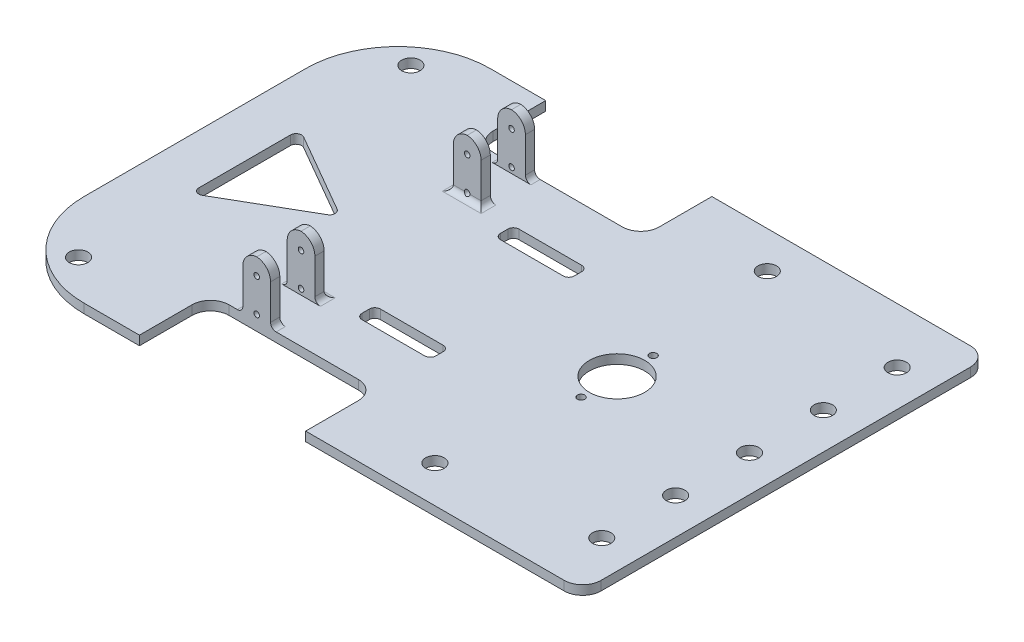
SolidWorks part; units mm, degrees
ref_plane "Front Plane" through (0, 0, 0) normal (0, 0, 1) x (1, 0, 0)
ref_plane "Top Plane" through (0, 0, 0) normal (0, 1, 0) x (1, 0, 0)
ref_plane "Right Plane" through (0, 0, 0) normal (1, 0, 0) x (0, 0, -1)
sketch "Sketch1" plane through (0, 0, 0) normal (0, 1, 0) x (1, 0, 0)
  line L1 (-160, 110) -> (160, 110)
  line L2 (-160, 110) -> (-160, -110)
  line L3 (-160, -110) -> (160, -110)
  line L4 (160, 110) -> (160, -110)
  line L5 (-160, 110) -> (160, -110) construction
  line L6 (-160, -110) -> (160, 110) construction
  point P1 (0, 0)
  dimension "D1" = 320
  dimension "D2" = 220
extrude "Boss-Extrude1" add sketch "Sketch1" along normal mid plane 5
sketch "Sketch2" plane through (0, 0, 0) normal (0, 1, 0) x (1, 0, 0)
  line L0 (0, 110) -> (0, -110) construction
  line L1 (160, 110) -> (-160, 110) construction
  line L2 (-160, -110) -> (160, -110) construction
  line L3 (160, 0) -> (-160, 0) construction
  line L4 (160, -110) -> (160, 110) construction
  line L5 (-160, 110) -> (-160, -110) construction
  line L6 (-133, 90) -> (-133, 0) construction
  line L7 (-133, -90) -> (-133, 0) construction
  line L8 (-160, 110) -> (-160, -110) construction
  line L10 (60, 90) -> (60, -90) construction
  line L11 (160, -110) -> (160, 110) construction
  circle A0 centre (-133, 90) radius 5
  circle A1 centre (-133, -90) radius 5
  circle A2 centre (60, 90) radius 5
  circle A3 centre (60, -90) radius 5
  dimension "D2" = 10
  dimension "D3" = 10
  dimension "D5" = 10
  dimension "D6" = 10
  dimension "D1" = 20
  dimension "D4" = 27
  dimension "D7" = 100
extrude "Cut-Extrude1" cut sketch "Sketch2" along direction (0, 1, 0) on the side against the normal mid plane 5
fillet "Fillet5" radius 50 2 edges at (-160, 0, -110) (-160, 0, 110)
sketch "Sketch3" plane through (0, 0, 0) normal (0, 1, 0) x (1, 0, 0)
  line L0 (160, 0) -> (-160, 0) construction
  line L1 (160, -110) -> (160, 110) construction
  line L2 (-160, 60) -> (-160, -60) construction
  line L3 (-80, 110) -> (-80, 71.5023)
  line L4 (160, 110) -> (-110, 110) construction
  line L5 (-80, 71.5023) -> (10, 71.5023)
  line L6 (10, 71.5023) -> (10, 110)
  line L7 (10, 110) -> (-80, 110)
  line L8 (10, -71.5023) -> (10, -110)
  line L9 (-80, -110) -> (-80, -71.5023)
  line L10 (-80, -71.5023) -> (10, -71.5023)
  line L11 (10, -110) -> (-80, -110)
  dimension "D1" = 90
  dimension "D2" = 80
extrude "Cut-Extrude2" cut sketch "Sketch3" against normal mid plane 5
fillet "Fillet3" radius 10 4 edges at (10, 0, 71.5023) (-80, 0, 71.5023) (-80, 0, -71.5023) (10, 0, -71.5023)
sketch "Sketch4" plane through (0, 0, 0) normal (0, 1, 0) x (1, 0, 0)
  line L0 (160, 0) -> (-160, 0) construction
  line L1 (160, -110) -> (160, 110) construction
  line L2 (-160, 60) -> (-160, -60) construction
  line L6 (68.6574, 19.5) -> (68.6574, 0) construction
  line L7 (68.6574, 0) -> (68.6574, -19.5) construction
  circle A0 centre (68.6574, 0) radius 15
  circle A1 centre (68.6574, 19.5) radius 2
  circle A2 centre (68.6574, -19.5) radius 2
  dimension "D1" = 30
  dimension "D2" = 2
  dimension "D3" = 4
  dimension "D4" = 39
extrude "middle hole" cut sketch "Sketch4" against normal mid plane 5
sketch "Sketch6" plane through (0, 0, 0) normal (0, 1, 0) x (1, 0, 0)
  line L0 (160, 0) -> (-160, 0) construction
  line L1 (160, -110) -> (160, 110) construction
  line L2 (-160, 60) -> (-160, -60) construction
  circle A0 centre (140.3612, 0) radius 5
  dimension "D1" = 10
extrude "Cut-Extrude4" cut sketch "Sketch6" against normal mid plane 5
pattern_linear "LPattern1" count 3 spacing 40 along (0, 0, -1) of "Cut-Extrude4"
pattern_linear "LPattern2" count 3 spacing 40 along (0, 0, 1) of "Cut-Extrude4"
sketch "Sketch8" plane through (0, 2.5, 0) normal (0, 1, 0) x (1, 0, 0)
  line L0 (0, -71.5023) -> (-70, -71.5023) construction
  line L1 (-62.5, -71.5023) -> (-47.5, -71.5023)
  line L2 (-62.5, -71.5023) -> (-62.5, -66.5023)
  line L3 (-62.5, -66.5023) -> (-47.5, -66.5023)
  line L4 (-47.5, -71.5023) -> (-47.5, -66.5023)
  line L6 (160, 0) -> (-160, 0) construction
  line L7 (160, -110) -> (160, 110) construction
  line L8 (-160, 60) -> (-160, -60) construction
  line L13 (-160, -47.5023) -> (160, -47.5023) construction
  line L14 (160, -110) -> (160, 110) construction
  line L15 (-55, -66.5023) -> (-55, -47.5023) construction
  line L16 (-55, -57.0023) -> (-160, -57.0023) construction
  line L17 (-47.5, -42.5023) -> (-47.5, -47.5023)
  line L18 (-62.5, -47.5023) -> (-47.5, -47.5023)
  line L19 (-62.5, -42.5023) -> (-62.5, -47.5023)
  line L20 (-62.5, -42.5023) -> (-47.5, -42.5023)
  line L21 (-55, 57.0023) -> (-160, 57.0023) construction
  line L22 (-55, 66.5023) -> (-55, 47.5023) construction
  line L23 (-160, 47.5023) -> (160, 47.5023) construction
  line L24 (-62.5, 42.5023) -> (-47.5, 42.5023)
  line L25 (-62.5, 42.5023) -> (-62.5, 47.5023)
  line L26 (-62.5, 47.5023) -> (-47.5, 47.5023)
  line L27 (-47.5, 42.5023) -> (-47.5, 47.5023)
  line L28 (-47.5, 71.5023) -> (-47.5, 66.5023)
  line L29 (-62.5, 66.5023) -> (-47.5, 66.5023)
  line L30 (-62.5, 71.5023) -> (-62.5, 66.5023)
  line L31 (-62.5, 71.5023) -> (-47.5, 71.5023)
  line L32 (10, -110) -> (-80, -110) construction
  line L33 (-35, -110) -> (-35, 0) construction
  point P22 (-55, -66.5023)
  point P47 (-55, -71.5023)
  dimension "D1" = 5
  dimension "D3" = 15
  dimension "D4" = 19
  dimension "D5" = 20
  dimension "D2" = 27.5
extrude "Boss-Extrude2" add sketch "Sketch8" along normal blind 30
sketch "Sketch10" plane through (0, 0, 0) normal (0, 1, 0) x (1, 0, 0)
  line L0 (10, -110) -> (10, -81.5023) construction
  line L1 (-30, -32.5023) -> (10, -32.5023)
  line L2 (-30, -32.5023) -> (-30, -42.5023)
  line L3 (-30, -42.5023) -> (10, -42.5023)
  line L4 (10, -32.5023) -> (10, -42.5023)
  line L5 (-160, 60) -> (-160, -60) construction
  line L6 (-160, 0) -> (160, 0) construction
  line L7 (160, -110) -> (160, 110) construction
  line L8 (10, 32.5023) -> (10, 42.5023)
  line L9 (-30, 42.5023) -> (10, 42.5023)
  line L10 (-30, 32.5023) -> (-30, 42.5023)
  line L11 (-30, 32.5023) -> (10, 32.5023)
  line L12 (-47.5, -42.5023) -> (-62.5, -42.5023) construction
  dimension "D3" = 40
  dimension "D4" = 10
extrude "Cut-Extrude6" cut sketch "Sketch10" against normal mid plane 67.5
sketch "Sketch9" plane through (0, 0, 71.5023) normal (0, 0, 1) x (1, 0, 0)
  line L0 (-55, 32.5) -> (-55, -2.5) construction
  line L1 (-62.5, 32.5) -> (-47.5, 32.5) construction
  line L2 (0, -2.5) -> (-70, -2.5) construction
  line L3 (0, 2.5) -> (-47.5, 2.5) construction
  circle A0 centre (-55, 23.5) radius 1.5
  circle A1 centre (-55, 5.5) radius 1.5
  dimension "D1" = 3
  dimension "D2" = 3
  dimension "D3" = 3
  dimension "D4" = 18
extrude "Cut-Extrude5" cut sketch "Sketch9" against normal up to surface (143.0046 mm away) up to face at (-45, 8.75, -71.5023)
fillet "Fillet6" radius 8 8 edges at (-62.5, 32.5, 69.0023) (-47.5, 32.5, 69.0023) (-47.5, 32.5, -69.0023) (-62.5, 32.5, -69.0023) (-62.5, 32.5, -45.0023) (-47.5, 32.5, -45.0023) (-47.5, 32.5, 45.0023) (-62.5, 32.5, 45.0023)
fillet "Fillet7" radius 10 2 edges at (160, 0, 110) (160, 0, -110)
fillet "Fillet8" radius 3 8 edges at (-30, 0, 32.5023) (-30, 0, 42.5023) (-30, 0, -42.5023) (-30, 0, -32.5023) (10, 0, -32.5023) (10, 0, 32.5023) (10, 0, -42.5023) (10, 0, 42.5023)
sketch "Sketch11" plane through (0, 0, 0) normal (0, 1, 0) x (1, 0, 0)
  line L0 (-160, 0) -> (160, 0) construction
  line L1 (-160, 60) -> (-160, -60) construction
  line L2 (160, -100) -> (160, 100) construction
  line L3 (-81.0385, 0) -> (-133, 30)
  line L4 (-133, 30) -> (-133, -30)
  line L5 (-133, -30) -> (-81.0385, 0)
  line L6 (-133, 90) -> (-133, -90) construction
  dimension "D1" = 60
extrude "Cut-Extrude7" cut sketch "Sketch11" against normal mid plane 10
fillet "Fillet9" radius 3 3 edges at (-133, 0, 30) (-133, 0, -30) (-81.0385, 0, 0)
sketch "Sketch12" plane through (0, 0, 0) normal (0, 1, 0) x (1, 0, 0)
  line L0 (-133, 90) -> (-133, -90) construction
fillet "Fillet10" radius 3 10 edges at (-62.5, 2.5, -45.0023) (-62.5, 2.5, -69.0023) (-55, 2.5, -42.5023) (-55, 2.5, 42.5023) (-62.5, 2.5, 45.0023) (-47.5, 2.5, 45.0023) (-47.5, 2.5, -69.0023) (-47.5, 2.5, -45.0023) (-62.5, 2.5, 69.0023) (-47.5, 2.5, 69.0023)
equation "\"carW\"= 22cm"
equation "\"carL\"= 32cm"
equation "\"D1@Sketch1\"=\"carL\""
equation "\"D2@Sketch1\"=\"carW\""
equation "\"carT\"= .5cm'car thickness"
equation "\"D1@Boss-Extrude1\"=\"carT\""
equation "\"linkNialDim\"= 10mm"
equation "\"D2@Sketch2\"=\"linkNialDim\""
equation "\"D3@Sketch2\"=\"linkNialDim\""
equation "\"D1@Sketch8\"=\"carT\""
equation "\"D5@Sketch2\"=\"linkNialDim\""
equation "\"D6@Sketch2\"=\"linkNialDim\""
